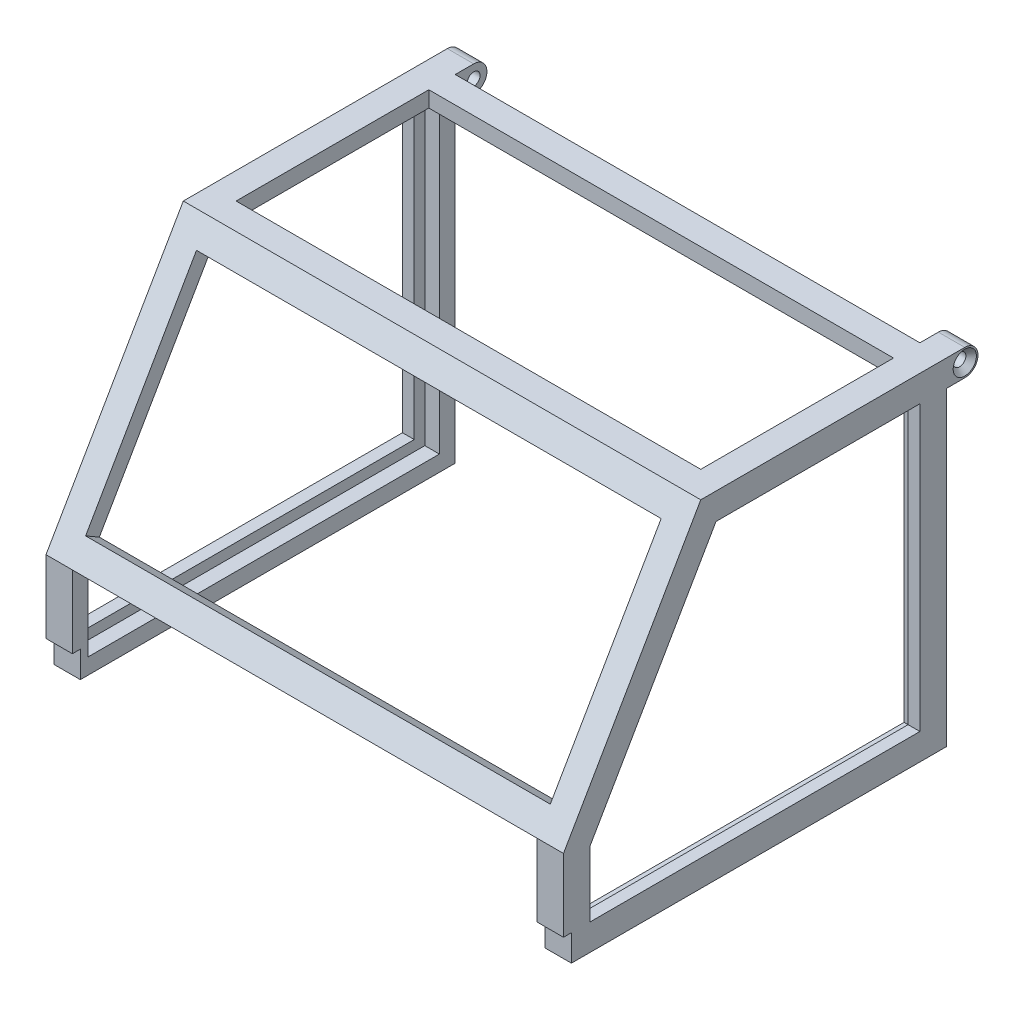
SolidWorks part; units mm, degrees
ref_plane "Front Plane" through (0, 0, 0) normal (0, 0, 1) x (1, 0, 0)
ref_plane "Top Plane" through (0, 0, 0) normal (0, 1, 0) x (1, 0, 0)
ref_plane "Right Plane" through (0, 0, 0) normal (1, 0, 0) x (0, 0, -1)
sketch "Sketch1" plane through (0, 0, 0) normal (1, 0, 0) x (0, 0, -1)
  line L0 (-36.25, 0.2437) -> (36.25, 0.2437)
  line L1 (36.25, 0.2437) -> (36.25, 58.9937)
  line L2 (36.25, 58.9937) -> (39.75, 58.9937)
  line L3 (39.75, 58.9937) -> (39.75, 61.4937) construction
  line L4 (39.75, 63.9937) -> (36.25, 63.9937)
  line L5 (36.25, 63.9937) -> (-10.25, 63.9937)
  line L6 (-36.25, 0.2437) -> (-36.25, 18.9937)
  line L7 (-36.25, 18.9937) -> (-10.25, 63.9937)
  line L8 (36.25, 0.2437) -> (31.25, 0.2437) construction
  line L9 (31.25, 0.2437) -> (31.25, 5.2437) construction
  line L12 (31.25, 5.2437) -> (-31.25, 5.2437)
  line L19 (31.25, 63.9937) -> (31.25, 58.9937) construction
  line L20 (31.25, 5.2437) -> (31.25, 58.9937)
  line L23 (-23.25, 41.4937) -> (-18.9207, 38.9924) construction
  line L24 (-18.9207, 38.9924) -> (-7.3643, 58.9937)
  line L27 (-18.9207, 38.9924) -> (-31.25, 17.6531)
  line L28 (-31.25, 5.2437) -> (-31.25, 17.6531)
  line L29 (-7.3643, 58.9937) -> (31.25, 58.9937)
  arc A0 (39.75, 58.9937) -> (39.75, 63.9937) centre (39.75, 61.4937) ccw
  point P3 (0, 0.2437)
extrude "Boss-Extrude1" add sketch "Sketch1" along normal blind 5
sketch "Sketch2" plane through (0, 0, 0) normal (-1, 0, 0) x (0, 0, 1)
  line L0 (-42.25, 61.4937) -> (-39.75, 61.4937) construction
hole_wizard "CSK for M2 Oval Head Machine Screw1" positions "Sketch3" profile "Sketch4" countersink size "M2" standard "ANSI Metric" end condition through all
sketch "Sketch3" plane through (0, 0, 0) normal (-1, 0, 0) x (0, 0, 1)
  point P0 (-39.75, 61.4937)
sketch "Sketch4" plane through (0, 61.4937, -39.75) normal (0, 1, 0) x (0, 0, 1)
  line L0 (0, 0) -> (0, 5)
  line L1 (0, 5) -> (1.2, 5)
  line L2 (1.2, 5) -> (1.2, 1)
  line L3 (1.2, 1) -> (2.2, 0)
  line L5 (2.2, 0) -> (0, 0)
  line L6 (-1.2, 1) -> (-2.2, 0) construction
  line L11 (0, -6.35) -> (0, 107.95) construction
  dimension "Thru Hole Dia." = 2.4
  dimension "Thru Hole Depth" = 5
  dimension "Near C'Sink Dia." = 4.4
  dimension "Near C'Sink Angle" = 90
sketch "Sketch6" plane through (5, 0, 0) normal (1, 0, 0) x (0, 0, -1)
  line L0 (31.25, 58.9937) -> (31.25, 60.9937) construction
  line L1 (31.25, 60.9937) -> (33.25, 60.9937) construction
  line L2 (33.25, 60.9937) -> (33.25, 3.2437)
  line L3 (33.25, 3.2437) -> (-33.25, 3.2437)
  line L4 (-23.25, 41.4937) -> (-20.6524, 39.9929) construction
  line L7 (-31.25, 13.2412) -> (-33.25, 13.2412) construction
  line L8 (-4.0306, 58.9937) -> (-4.0306, 60.9937) construction
  line L9 (-33.25, 3.2437) -> (-33.25, 18.1894)
  line L10 (-33.25, 18.1894) -> (-8.5186, 60.9937)
  line L11 (-8.5186, 60.9937) -> (33.25, 60.9937)
extrude "Cut-Extrude1" cut sketch "Sketch6" against normal blind 2.762
sketch "Sketch9" plane through (0, 0, 36.25) normal (0, 0, 1) x (1, 0, 0)
  line L5 (5, 0.2437) -> (0, 0.2437)
  line L6 (5, 0.2437) -> (5, 5.2437)
  line L7 (5, 5.2437) -> (0, 5.2437)
  line L8 (0, 0.2437) -> (0, 5.2437)
extrude "Cut-Extrude3" cut sketch "Sketch9" against normal blind 1.5
sketch "Sketch10" plane through (5, 0, 0) normal (1, 0, 0) x (0, 0, -1)
  line L0 (-10.25, 63.9937) -> (-5.25, 63.9937)
  line L1 (-5.25, 63.9937) -> (-5.25, 60.9937)
  line L2 (-5.25, 60.9937) -> (-8.5186, 60.9937)
  line L3 (-10.25, 63.9937) -> (-12.7514, 59.6644)
  line L4 (-12.7514, 59.6644) -> (-10.1538, 58.1636)
  line L5 (-10.1538, 58.1636) -> (-8.5186, 60.9937)
  line L6 (36.25, 58.9937) -> (36.25, 63.9937)
  line L7 (36.25, 63.9937) -> (31.25, 63.9937)
  line L8 (31.25, 63.9937) -> (31.25, 60.9937)
  line L9 (31.25, 60.9937) -> (33.25, 60.9937)
  line L10 (33.25, 60.9937) -> (33.25, 58.9937)
  line L11 (33.25, 58.9937) -> (36.25, 58.9937)
  line L12 (-36.25, 18.9937) -> (-33.7486, 23.3231)
  line L13 (-33.7486, 23.3231) -> (-31.151, 21.8222)
  line L18 (-31.151, 21.8222) -> (-32.7853, 18.9937)
  line L19 (-32.7853, 18.9937) -> (-36.25, 18.9937)
extrude "Boss-Extrude2" add sketch "Sketch10" along normal blind 44
sketch "Sketch14" plane through (2.238, 0, 0) normal (1, 0, 0) x (0, 0, -1)
  line L0 (-32.7853, 18.9937) -> (-30.4754, 18.9937)
  line L1 (-30.4754, 18.9937) -> (-29.9733, 19.8627)
  line L2 (-29.9733, 19.8627) -> (-31.7051, 20.8633)
  line L3 (-31.7051, 20.8633) -> (-32.7853, 18.9937)
extrude "Boss-Extrude5" add sketch "Sketch14" along normal blind 44.5 from offset 2.76
ref_axis "Axis1" through (49, 59.6644, 12.7514) along (0, -0.5003, -0.8659)
mirror "Mirror1" about plane through (49, 0, 0) normal (1, 0, 0) of bodies 113
